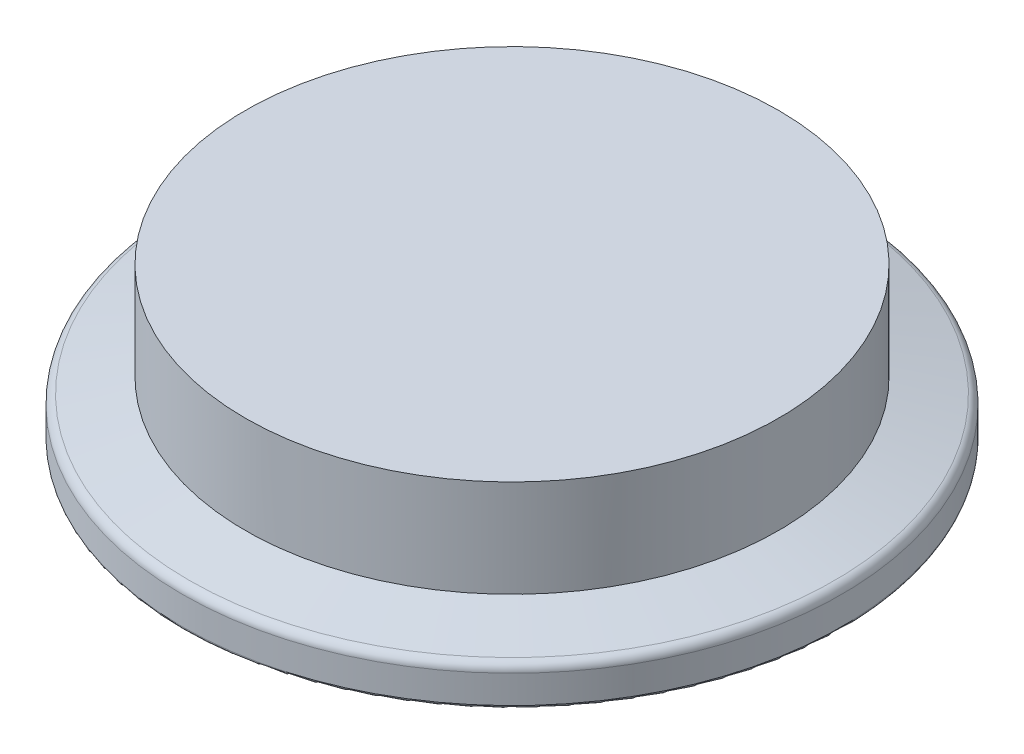
SolidWorks part; units mm, degrees
material "AISI 304"
ref_plane "Front Plane" through (0, 0, 0) normal (0, 0, 1) x (1, 0, 0)
ref_plane "Top Plane" through (0, 0, 0) normal (0, 1, 0) x (1, 0, 0)
ref_plane "Right Plane" through (0, 0, 0) normal (1, 0, 0) x (0, 0, -1)
sketch "Sketch1" plane through (0, 0, 0) normal (1, 0, 0) x (0, 0, -1)
  line L0 (0, 0) -> (0, 5.1) construction
  line L1 (-27.5, 0) -> (-27.5, 3.175)
  line L2 (-27.5, 3.175) -> (-20.3158, 5.1)
  line L6 (0, 2.5) -> (-20.625, 2.5)
  line L7 (-20.625, 2.5) -> (-20.625, 0)
  line L8 (-20.625, 0) -> (-27.5, 0)
  line L9 (-20.3158, 5.1) -> (0, 5.1)
  line L10 (0, 5.1) -> (0, 2.5)
  dimension "D1" = 75
  dimension "D2" = 40.6316
  dimension "Flange ID" = 41.25
  dimension "Flange OD" = 55
  dimension "D5" = 3.175
  dimension "Flange Height" = 5.1
  dimension "D9" = 2.5
revolve "Flange" add sketch "Sketch1" angle 360 about L0
sketch "Sketch2" plane through (0, 0, 0) normal (1, 0, 0) x (0, 0, -1)
  line L0 (0, 2.5) -> (-20.625, 2.5) construction
  line L1 (0, 0) -> (-15.85, 0)
  line L2 (0, 0) -> (0, 2.5)
  line L3 (0, 2.5) -> (-15.85, 2.5)
  line L4 (-15.85, 0) -> (-15.85, 2.5)
  line L5 (0, 0) -> (0, -4.8376) construction
  dimension "ID" = 31.7
revolve "Blank Insert" add sketch "Sketch2" angle 360 about L5
sketch "Sketch5" plane through (0, 2.5, 0) normal (0, -1, 0) x (1, 0, 0)
  circle A0 centre (0, 0) radius 22.25
  dimension "D1" = 44.5
extrude "Stub" add sketch "Sketch5" against normal offset from surface (10.2 mm away) 12.7 up to face at (0, 0, -20.625)
ref_plane "Plane1" through (0, -1.905, 0) normal (0, -1, 0) x (-1, 0, 0)
ref_plane "Plane2" through (0, 2.5, 0) normal (0, -1, 0) x (-1, 0, 0)
ref_plane "Plane3" through (0, 5.1, 0) normal (0, -1, 0) x (-1, 0, 0)
fillet "Fillet1" radius 0.762 1 edges at (0, 3.175, -27.5)
fillet "Fillet2" radius 0.254 1 edges at (0, 0, -27.5)
